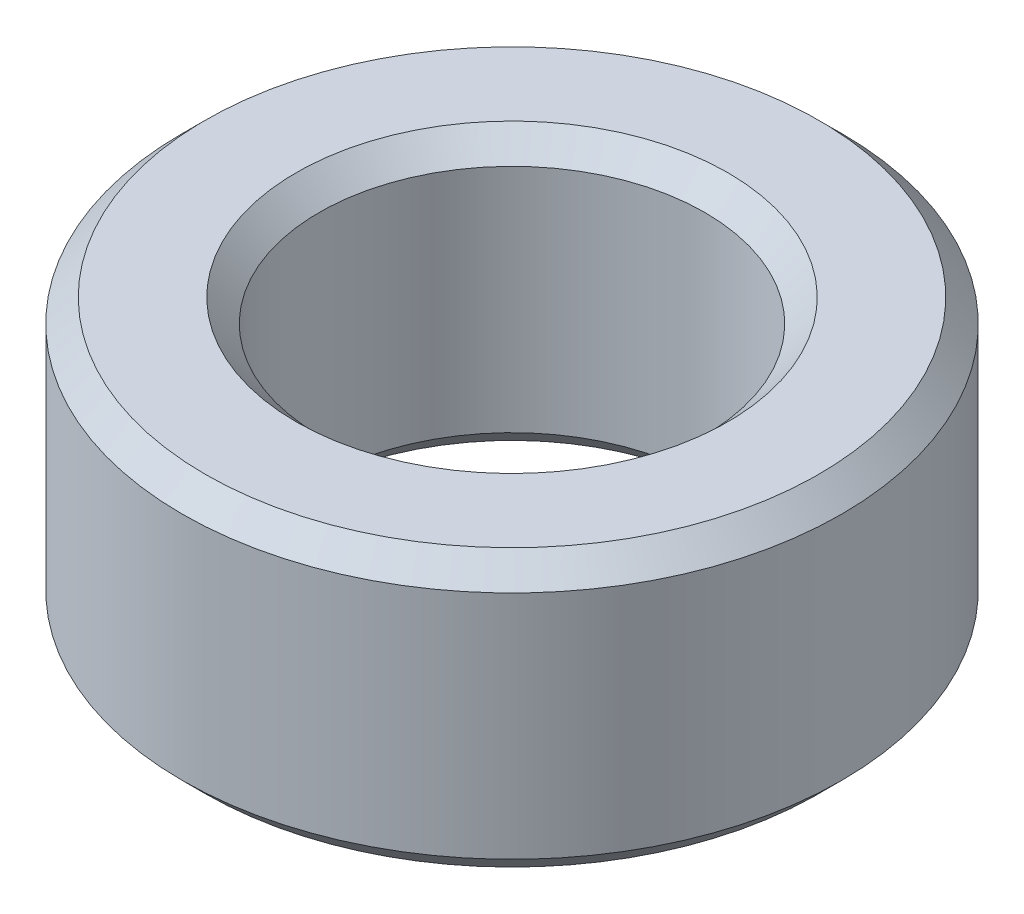
SolidWorks part; units mm, degrees
ref_plane "Front Plane" through (0, 0, 0) normal (0, 0, 1) x (1, 0, 0)
ref_plane "Top Plane" through (0, 0, 0) normal (0, 1, 0) x (1, 0, 0)
ref_plane "Right Plane" through (0, 0, 0) normal (1, 0, 0) x (0, 0, -1)
sketch "Sketch1" plane through (0, 0, 0) normal (0, 1, 0) x (1, 0, 0)
  circle A0 centre (0, 0) radius 15
  dimension "SLEEVE_OD" = 30
extrude "Boss-Extrude1" add sketch "Sketch1" along normal blind 12.5841
sketch "Sketch2" plane through (0, 0, 0) normal (0, 1, 0) x (1, 0, 0)
  circle A0 centre (0, 0) radius 8.7746
  dimension "BORE_D" = 17.5493
extrude "Cut-Extrude1" cut sketch "Sketch2" along normal through all
chamfer "Chamfer1" distance 1.0454 angle 45 4 edges at (0, 12.5841, 8.7746) (0, 0, 8.7746) (0, 0, 15) (0, 12.5841, 15)
